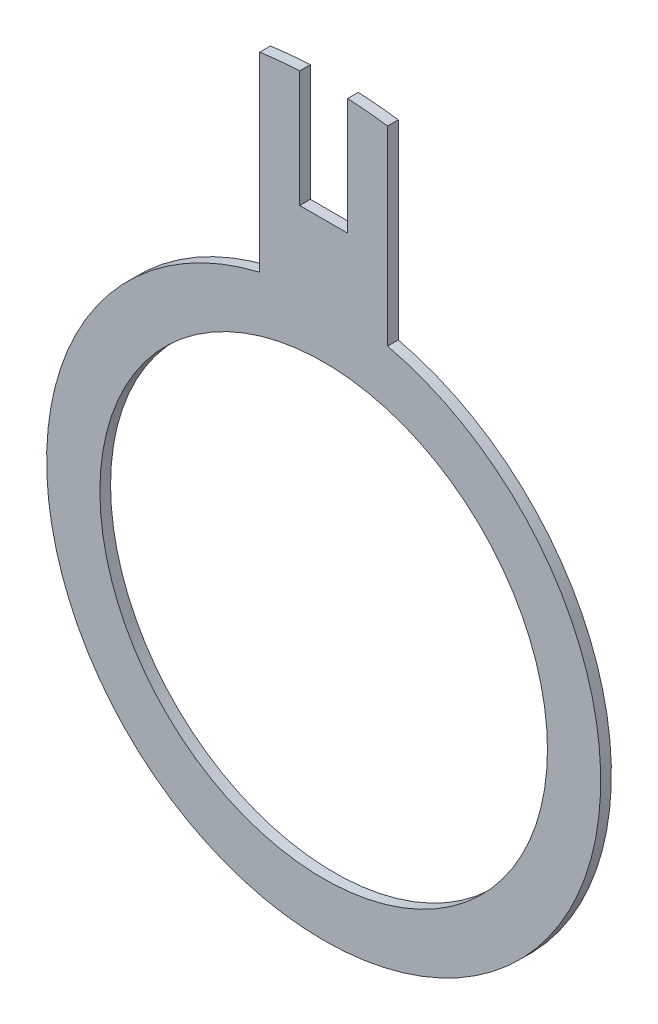
SolidWorks part; units mm, degrees
ref_plane "Alzado" through (0, 0, 0) normal (0, 0, 1) x (1, 0, 0)
ref_plane "Planta" through (0, 0, 0) normal (0, 1, 0) x (1, 0, 0)
ref_plane "Vista lateral" through (0, 0, 0) normal (1, 0, 0) x (0, 0, -1)
sketch "Sketch1" plane through (0, 0, 0) normal (0, 0, 1) x (1, 0, 0)
  line L0 (0, -1000) -> (0, 49000) construction
  line L1 (0.225, -1000.0033) -> (0.225, 48999.9967) construction
  line L2 (-0.225, -999.8572) -> (-0.225, 49000.1428) construction
  line L3 (-0.6, -999.7642) -> (-0.6, 49000.2358) construction
  line L4 (0.6, -999.9103) -> (0.6, 49000.0897) construction
  line L5 (-1000, 0) -> (49000, 0) construction
  line L6 (-1000.0861, 3.26) -> (48999.9139, 3.26) construction
  line L7 (-0.6, 2.5298) -> (-0.6, 4.3185)
  line L9 (-0.225, 4.3542) -> (-0.225, 3.26)
  line L11 (-0.225, 3.26) -> (0.225, 3.26)
  line L13 (0.225, 3.26) -> (0.225, 4.3542)
  line L15 (0.6, 4.3185) -> (0.6, 2.5298)
  arc A0 (-0.6, 2.5298) -> (0.6, 2.5298) centre (0, 0) ccw
  circle A1 centre (0, 0) radius 2.1
  circle A2 centre (0, 0) radius 4.36 construction
  arc A3 (-0.6, 4.3185) -> (-0.225, 4.3542) centre (0, 0) cw
  arc A4 (0.225, 4.3542) -> (0.6, 4.3185) centre (0, 0) cw
  dimension "D1" = 5.2
  dimension "D2" = 4.2
  dimension "D8" = 8.72
  dimension "D3" = 0.225
  dimension "D4" = 0.225
  dimension "D5" = 0.6
  dimension "D6" = 0.6
  dimension "D7" = 3.26
extrude "Boss-Extrude1" add sketch "Sketch1" along normal blind 0.1
sketch "Sketch3" plane through (0, 0, 0) normal (0, 0, 1) x (1, 0, 0)
  line L0 (0.225, 3.26) -> (-0.225, 3.26) construction
  line L1 (0, 3.26) -> (0, 4.3867)
  point P0 (0, 3.26)
ref_axis "Axis1" through (0, 3.26, 0) along (0, 1, 0)
